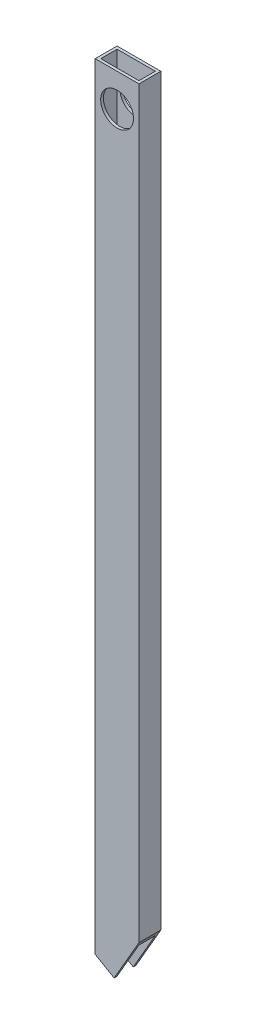
SolidWorks part; units mm, degrees
ref_plane "Front Plane" through (0, 0, 0) normal (0, 0, 1) x (1, 0, 0)
ref_plane "Top Plane" through (0, 0, 0) normal (0, 1, 0) x (1, 0, 0)
ref_plane "Right Plane" through (0, 0, 0) normal (1, 0, 0) x (0, 0, -1)
sketch "Sketch1" plane through (0, 0, 0) normal (0, 1, 0) x (1, 0, 0)
  line L0 (-22.225, 9.525) -> (-22.225, 12.7) construction
  line L1 (-25.4, -12.7) -> (25.4, -12.7)
  line L2 (-25.4, -12.7) -> (-25.4, 12.7)
  line L3 (-25.4, 12.7) -> (25.4, 12.7)
  line L4 (25.4, -12.7) -> (25.4, 12.7)
  line L5 (-25.4, -12.7) -> (25.4, 12.7) construction
  line L6 (-25.4, 12.7) -> (25.4, -12.7) construction
  line L7 (-22.225, -9.525) -> (22.225, -9.525)
  line L8 (-22.225, -9.525) -> (-22.225, 9.525)
  line L9 (-22.225, 9.525) -> (22.225, 9.525)
  line L10 (22.225, -9.525) -> (22.225, 9.525)
  line L11 (-22.225, -9.525) -> (22.225, 9.525) construction
  line L12 (-22.225, 9.525) -> (22.225, -9.525) construction
  line L13 (-22.225, 9.525) -> (-25.4, 9.525) construction
  point P0 (0, 0)
  point P6 (0, 0)
  dimension "D1" = 3.175
  dimension "D2" = 50.8
  dimension "D3" = 25.4
extrude "Boss-Extrude1" add sketch "Sketch1" along normal blind 914.4
sketch "Sketch2" plane through (0, 0, 12.7) normal (0, 0, 1) x (1, 0, 0)
  line L9 (-25.4, 0) -> (-25.4, 12.7)
  line L10 (-25.4, 914.4) -> (-25.4, 0) construction
  line L11 (-25.4, 12.7) -> (-3.403, 0)
  line L12 (-25.4, 0) -> (25.4, 0) construction
  line L13 (-3.403, 0) -> (-25.4, 0)
  line L14 (25.4, 0) -> (-3.403, 0)
  line L15 (25.4, 0) -> (25.4, 49.8882)
  line L16 (25.4, 914.4) -> (25.4, 0) construction
  line L17 (25.4, 49.8882) -> (-3.403, 0)
  line L18 (-25.4, 914.4) -> (25.4, 914.4) construction
  circle A0 centre (0, 876.3) radius 19.05
  line M3 (-25.4, 0) -> (25.4, 0)
  line M4 (25.4, 0) -> (25.4, 914.4)
  line M6 (-25.4, 914.4) -> (-25.4, 0)
  dimension "D3" = 38.1
  dimension "D1" = 30
  dimension "D2" = 25.4
  dimension "D4" = 38.1
extrude "Cut-Extrude1" cut sketch "Sketch2" against normal through all contours L11 M6 M3 | L17 M4 M3 | A0 region at (15.799, 16.6294, 12.7) region at (-18.0677, 4.2333, 12.7)
